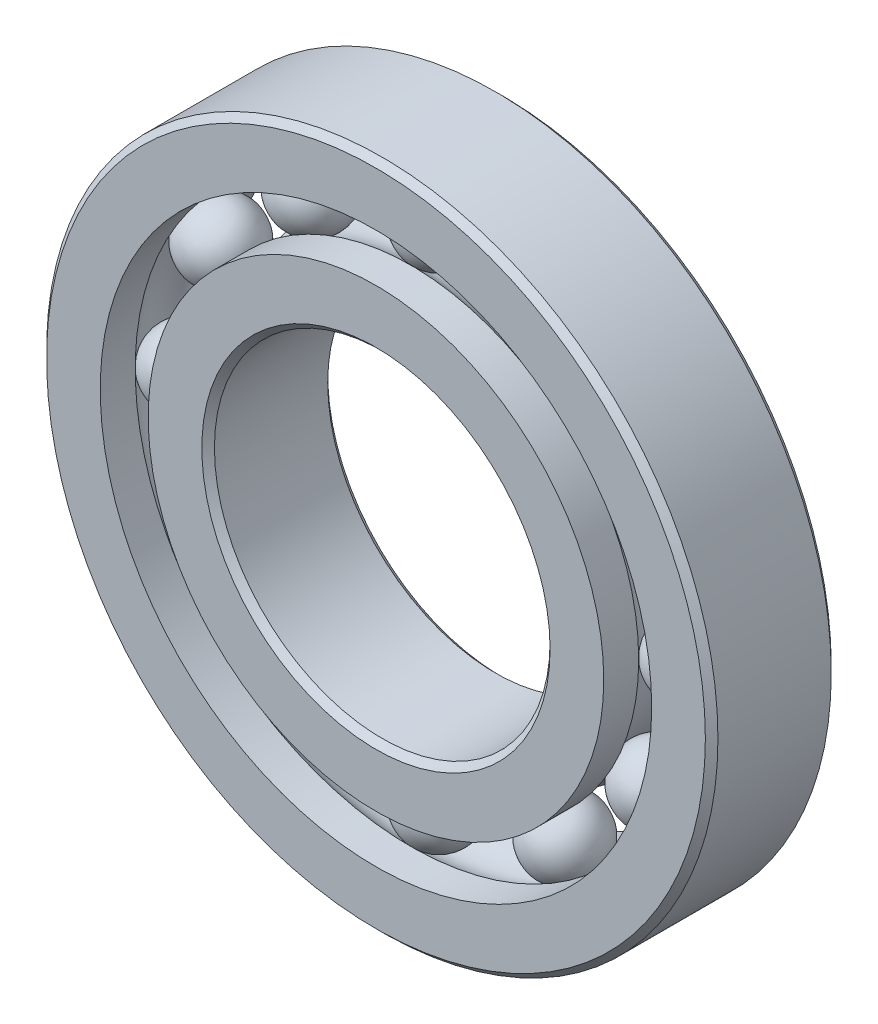
SolidWorks part; units mm, degrees
ref_plane "Front Plane" through (0, 0, 0) normal (0, 0, 1) x (1, 0, 0)
ref_plane "Top Plane" through (0, 0, 0) normal (0, 1, 0) x (1, 0, 0)
ref_plane "Right Plane" through (0, 0, 0) normal (1, 0, 0) x (0, 0, -1)
sketch "Sketch1" plane through (0, 0, 0) normal (1, 0, 0) x (0, 0, -1)
  line L0 (-4.7625, 0) -> (4.7625, 0) construction
  line L1 (0, 25.4) -> (0, -25.4) construction
  line L2 (4.2863, 25.4) -> (-4.2863, 25.4)
  line L3 (-4.2863, 25.4) -> (-4.7625, 24.9238)
  line L4 (-4.7625, 24.9238) -> (-4.7625, 20.8643)
  line L5 (-4.7625, 20.8643) -> (-2.1167, 20.8643)
  line L6 (4.7625, 20.8643) -> (2.1167, 20.8643)
  line L7 (4.7625, 24.9238) -> (4.7625, 20.8643)
  line L8 (4.2863, 25.4) -> (4.7625, 24.9238)
  line L9 (0, 25.4) -> (0, 19.05) construction
  line L10 (0, 19.05) -> (0, 12.7) construction
  arc A0 (-2.1167, 20.8643) -> (2.1167, 20.8643) centre (0, 19.05) cw
  point P14 (0, 12.7)
  dimension "Width" = 9.525
  dimension "OD" = 50.8
  dimension "D1" = 45
  dimension "D2" = 0.4763
  dimension "Shaft Dia" = 25.4
  dimension "D3" = 4.2333
  dimension "D4" = 1.8143
revolve "Revolve1" add sketch "Sketch1" angle 360 about L0
sketch "Sketch3" plane through (0, 0, 0) normal (1, 0, 0) x (0, 0, -1)
  line L0 (-4.7625, 17.2357) -> (-2.1167, 17.2357)
  line L1 (0, 25.4) -> (0, -25.4) construction
  line L2 (-4.7625, 24.9238) -> (-4.7625, 20.8643) construction
  line L3 (-4.7625, 17.2357) -> (-4.7625, 13.1762)
  line L4 (-4.2863, 25.4) -> (-4.7625, 24.9238) construction
  line L5 (-4.7625, 13.1762) -> (-4.2863, 12.7)
  line L6 (-4.2863, 12.7) -> (4.2862, 12.7)
  line L7 (4.2863, 25.4) -> (4.2863, -25.4) construction
  line L8 (4.2862, 12.7) -> (4.7625, 13.1762)
  line L9 (4.7625, -24.9238) -> (4.7625, 24.9238) construction
  line L10 (4.7625, 13.1762) -> (4.7625, 17.2357)
  line L11 (4.7625, 17.2357) -> (2.1167, 17.2357)
  line L13 (4.2863, 25.4) -> (4.7625, 24.9238) construction
  arc A0 (2.1167, 20.8643) -> (-2.1167, 20.8643) centre (0, 19.05) ccw construction
  arc A1 (2.1167, 17.2357) -> (-2.1167, 17.2357) centre (0, 19.05) cw
revolve "Revolve3" add sketch "Sketch3" angle 360 about L0
sketch "Sketch4" plane through (0, 0, 0) normal (1, 0, 0) x (0, 0, -1)
  line L0 (-2.7878, 19.05) -> (2.7878, 19.05)
  arc A2 (-2.7878, 19.05) -> (2.7878, 19.05) centre (0, 19.05) cw
  arc A3 (2.1167, 20.8643) -> (-2.1167, 20.8643) centre (0, 19.05) ccw construction
revolve "Revolve4" add sketch "Sketch4" angle 360 about L0
ref_axis "Axis1" through (0, 0, -4.7625) along (0, 0, 1)
pattern_circular "CirPattern1" count 12 every 30 about axis through (0, 0, -4.7625) along (0, 0, 1) of bodies 104
sketch "Sketch5" plane through (0, 0, 0) normal (1, 0, 0) x (0, 0, -1)
  line L0 (-4.7625, 20.8643) -> (-2.1167, 20.8643) construction
  line L1 (-4.5244, 20.8643) -> (-2.7878, 20.8643)
  line L2 (-4.5244, 20.8643) -> (-4.5244, 17.2357)
  line L3 (-4.5244, 17.2357) -> (-2.7878, 17.2357)
  line L4 (-2.7878, 20.8643) -> (-2.7878, 17.2357)
  line L5 (-4.7625, 17.2357) -> (-2.1167, 17.2357) construction
  line L6 (4.7625, 20.8643) -> (2.1167, 20.8643) construction
  line L7 (4.5244, 20.8643) -> (2.7878, 20.8643)
  line L8 (4.5244, 20.8643) -> (4.5244, 17.2357)
  line L9 (4.5244, 17.2357) -> (2.7878, 17.2357)
  line L10 (2.7878, 20.8643) -> (2.7878, 17.2357)
  line L11 (4.7625, 17.2357) -> (2.1167, 17.2357) construction
  line L12 (-4.2863, 25.4) -> (-4.7625, 24.9238) construction
  point P18 (-4.5244, 25.1619)
revolve "Revolve5" [suppressed] add sketch "Sketch5" angle 360 about L0
equation "\"D2@Sketch1\" = \"Width@Sketch1\"*.05"
equation "\"D3@Sketch1\" = \"Width@Sketch1\"/2.25"
equation "\"D4@Sketch1\" = (((\"OD@Sketch1\"-\"Width@Sketch1\")/2)/3.25)/3.5"
equation "\"D2@CirPattern1\" = 360/\"Balls@CirPattern1\""
